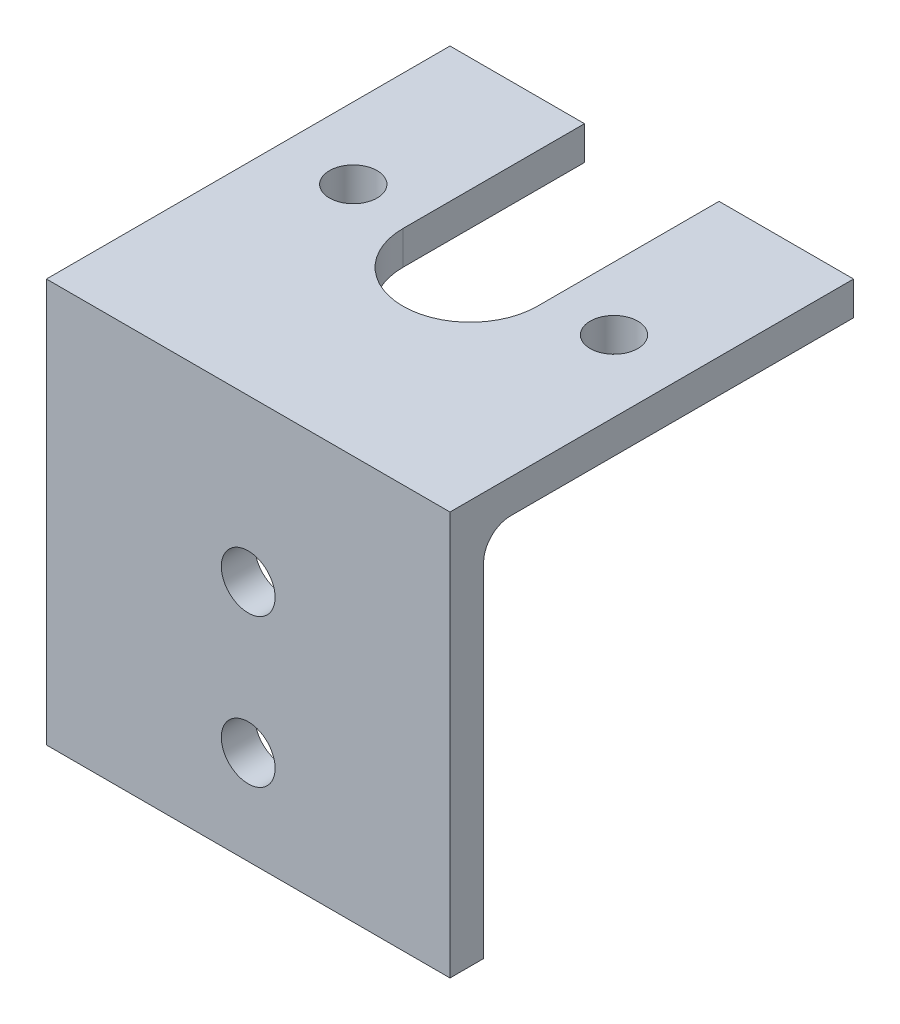
SolidWorks part; units mm, degrees
ref_plane "Front Plane" through (0, 0, 0) normal (0, 0, 1) x (1, 0, 0)
ref_plane "Top Plane" through (0, 0, 0) normal (0, 1, 0) x (1, 0, 0)
ref_plane "Right Plane" through (0, 0, 0) normal (1, 0, 0) x (0, 0, -1)
sketch "Sketch1" plane through (0, 0, 0) normal (0, 1, 0) x (1, 0, 0)
  line L0 (-19.5834, -8.6292) -> (18.5166, -8.6292) construction
  line L1 (-19.5834, 16.7708) -> (-6.8834, 16.7708) construction
  line L2 (-19.5834, 16.7708) -> (-19.5834, -14.9792)
  line L3 (-19.5834, -14.9792) -> (18.5166, -14.9792)
  line L4 (18.5166, 16.7708) -> (18.5166, -14.9792)
  line L5 (-19.5834, 4.0708) -> (18.5166, 4.0708) construction
  line L6 (-19.5834, 16.7708) -> (-19.5834, 19.9458)
  line L7 (-19.5834, 19.9458) -> (-6.8834, 19.9458)
  line L10 (-6.8834, -3.5492) -> (-6.8834, 16.7708)
  line L11 (5.8166, -3.5492) -> (5.8166, 16.7708)
  line L12 (5.8166, 16.7708) -> (18.5166, 16.7708) construction
  line L13 (-6.8834, -3.5492) -> (5.8166, -3.5492)
  line L14 (-6.8834, 19.9458) -> (-6.8834, 16.7708)
  line L15 (5.8166, 16.7708) -> (5.8166, 19.9458)
  line L16 (5.8166, 19.9458) -> (18.5166, 19.9458)
  line L17 (18.5166, 19.9458) -> (18.5166, 16.7708)
  circle A1 centre (-12.8397, 4.0708) radius 2.2479
  circle A2 centre (11.7729, 4.0708) radius 2.2479
  dimension "D1" = 25.4
  dimension "D4" = 4.4958
  dimension "D5" = 4.4958
  dimension "D2" = 38.1
  dimension "D3" = 31.75
  dimension "D6" = 6.7437
  dimension "D7" = 6.7437
  dimension "D8" = 12.7
  dimension "D9" = 12.7
  dimension "D10" = 7.62
  dimension "D11" = 3.175
  dimension "D12" = 12.7
extrude "Boss-Extrude1" add sketch "Sketch1" along normal blind 3.175
fillet "Fillet1" radius 6.35 2 edges at (5.8166, 1.5875, 3.5492) (-6.8834, 1.5875, 3.5492)
sketch "Sketch2" plane through (0, 0, 14.9792) normal (0, 0, 1) x (1, 0, 0)
  line L0 (18.5166, 3.175) -> (18.5166, 0) construction
  line L1 (-19.5834, 3.175) -> (18.5166, 3.175)
  line L2 (-19.5834, 3.175) -> (-19.5834, -34.925)
  line L3 (-19.5834, -34.925) -> (18.5166, -34.925)
  line L4 (18.5166, 3.175) -> (18.5166, -34.925)
  line L5 (-0.5334, 3.175) -> (-0.5334, -34.925) construction
  circle A0 centre (-0.5334, -12.065) radius 2.54
  circle A1 centre (-0.5334, -26.035) radius 2.54
  dimension "D2" = 5.08
  dimension "D3" = 5.08
  dimension "D1" = 38.1
  dimension "D4" = 13.97
  dimension "D5" = 15.24
extrude "Boss-Extrude2" add sketch "Sketch2" along normal blind 3.175
fillet "Fillet2" radius 2.54 1 edges at (-0.5334, 0, 14.9792)
